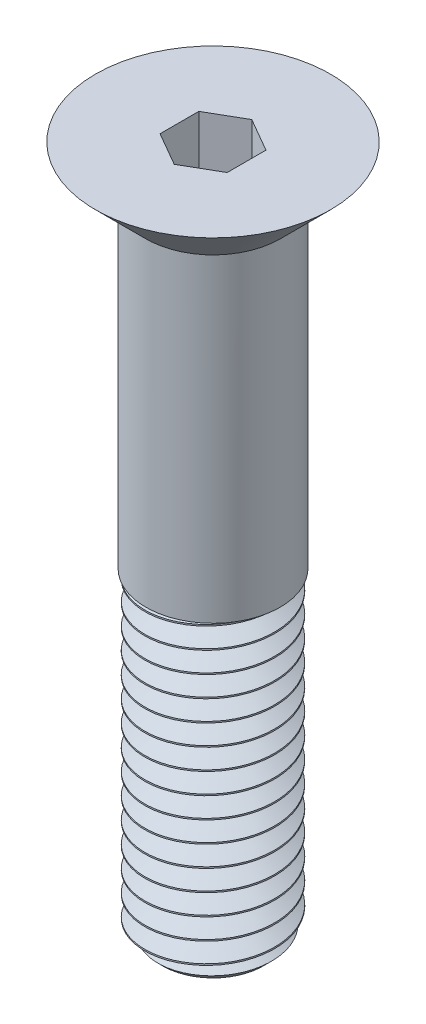
SolidWorks part; units mm, degrees
ref_plane "Front Plane" through (0, 0, 0) normal (0, 0, 1) x (1, 0, 0)
ref_plane "Top Plane" through (0, 0, 0) normal (0, 1, 0) x (1, 0, 0)
ref_plane "Right Plane" through (0, 0, 0) normal (1, 0, 0) x (0, 0, -1)
sketch "Sketch1" plane through (0, 0, 0) normal (0, 1, 0) x (1, 0, 0)
  circle A0 centre (0, 0) radius 4
  circle A1 centre (0, 0) radius 1
  dimension "D1" = 8
  dimension "D2" = 2
extrude "Boss-Extrude1" add sketch "Sketch1" along normal blind 19
ref_plane "Plane1" through (0, 29, 0) normal (0, 1, 0) x (1, 0, 0)
sketch "Sketch2" plane through (0, 29, 0) normal (0, 1, 0) x (1, 0, 0)
  circle A0 centre (0, 0) radius 4
  dimension "D1" = 8
curve "Helix/Spiral1" pitch 1.25 height 30 radius 4 centre (0, 29, 0) axis (0, -1, 0) start towards (0, 0, 1)
chamfer "Chamfer1" distance 1 angle 45 1 edges at (0, 0, 4)
sketch "Sketch3" plane through (0, 0, 0) normal (0, 0, 1) x (1, 0, 0)
  line L3 (-3.9386, 25.2152) -> (-3.9386, 25.8402) construction
  line L4 (-3.9386, 25.2152) -> (-3.9386, 24.5902) construction
  line L5 (-3.9386, 25.8402) -> (-3.9386, 24.5902)
  line L6 (-3.9386, 24.5902) -> (-2.8561, 25.2152)
  line L7 (-2.8561, 25.2152) -> (-3.9386, 25.8402)
  spline S0 degree 3 poles (-4, 29) (-4, 28.9741) (-3.7917, 28.9218) (-2.9021, 28.8438) (-1.5706, 28.7656) (0, 28.6875) (1.5706, 28.6094) (2.9021, 28.5313) (3.7917, 28.4531) (4.1041, 28.375) (3.7917, 28.2969) (2.9021, 28.2188) (1.5706, 28.1406) (0, 28.0625) (-1.5706, 27.9844) (-2.9021, 27.9063) (-3.7917, 27.8281) (-4.1041, 27.75) (-3.7917, 27.6719) (-2.9021, 27.5938) (-1.5706, 27.5156) (0, 27.4375) (1.5706, 27.3594) (2.9021, 27.2812) (3.7917, 27.2031) (4.1041, 27.125) (3.7917, 27.0469) (2.9021, 26.9688) (1.5706, 26.8906) (0, 26.8125) (-1.5706, 26.7344) (-2.9021, 26.6562) (-3.7917, 26.5781) (-4.1041, 26.5) (-3.7917, 26.4219) (-2.9021, 26.3437) (-1.5706, 26.2656) (0, 26.1875) (1.5706, 26.1094) (2.9021, 26.0312) (3.7917, 25.9531) (4.1041, 25.875) (3.7917, 25.7969) (2.9021, 25.7187) (1.5706, 25.6406) (0, 25.5625) (-1.5706, 25.4844) (-2.9021, 25.4062) (-3.7917, 25.3281) (-4.1041, 25.25) (-3.7917, 25.1719) (-2.9021, 25.0938) (-1.5706, 25.0156) (0, 24.9375) (1.5706, 24.8594) (2.9021, 24.7812) (3.7917, 24.7031) (4.1041, 24.625) (3.7917, 24.5469) (2.9021, 24.4688) (1.5706, 24.3906) (0, 24.3125) (-1.5706, 24.2344) (-2.9021, 24.1562) (-3.7917, 24.0781) (-4.1041, 24) (-3.7917, 23.9219) (-2.9021, 23.8437) (-1.5706, 23.7656) (0, 23.6875) (1.5706, 23.6094) (2.9021, 23.5312) (3.7917, 23.4531) (4.1041, 23.375) (3.7917, 23.2969) (2.9021, 23.2187) (1.5706, 23.1406) (0, 23.0625) (-1.5706, 22.9844) (-2.9021, 22.9062) (-3.7917, 22.8281) (-4.1041, 22.75) (-3.7917, 22.6719) (-2.9021, 22.5937) (-1.5706, 22.5156) (0, 22.4375) (1.5706, 22.3594) (2.9021, 22.2812) (3.7917, 22.2031) (4.1041, 22.125) (3.7917, 22.0469) (2.9021, 21.9688) (1.5706, 21.8906) (0, 21.8125) (-1.5706, 21.7344) (-2.9021, 21.6562) (-3.7917, 21.5781) (-4.1041, 21.5) (-3.7917, 21.4219) (-2.9021, 21.3438) (-1.5706, 21.2656) (0, 21.1875) (1.5706, 21.1094) (2.9021, 21.0312) (3.7917, 20.9531) (4.1041, 20.875) (3.7917, 20.7969) (2.9021, 20.7188) (1.5706, 20.6406) (0, 20.5625) (-1.5706, 20.4844) (-2.9021, 20.4062) (-3.7917, 20.3281) (-4.1041, 20.25) (-3.7917, 20.1719) (-2.9021, 20.0937) (-1.5706, 20.0156) (0, 19.9375) (1.5706, 19.8594) (2.9021, 19.7812) (3.7917, 19.7031) (4.1041, 19.625) (3.7917, 19.5469) (2.9021, 19.4687) (1.5706, 19.3906) (0, 19.3125) (-1.5706, 19.2344) (-2.9021, 19.1562) (-3.7917, 19.0781) (-4.1041, 19) (-3.7917, 18.9219) (-2.9021, 18.8437) (-1.5706, 18.7656) (0, 18.6875) (1.5706, 18.6094) (2.9021, 18.5312) (3.7917, 18.4531) (4.1041, 18.375) (3.7917, 18.2969) (2.9021, 18.2187) (1.5706, 18.1406) (0, 18.0625) (-1.5706, 17.9844) (-2.9021, 17.9062) (-3.7917, 17.8281) (-4.1041, 17.75) (-3.7917, 17.6719) (-2.9021, 17.5937) (-1.5706, 17.5156) (0, 17.4375) (1.5706, 17.3594) (2.9021, 17.2812) (3.7917, 17.2031) (4.1041, 17.125) (3.7917, 17.0469) (2.9021, 16.9687) (1.5706, 16.8906) (0, 16.8125) (-1.5706, 16.7344) (-2.9021, 16.6562) (-3.7917, 16.5781) (-4.1041, 16.5) (-3.7917, 16.4219) (-2.9021, 16.3437) (-1.5706, 16.2656) (0, 16.1875) (1.5706, 16.1094) (2.9021, 16.0312) (3.7917, 15.9531) (4.1041, 15.875) (3.7917, 15.7969) (2.9021, 15.7187) (1.5706, 15.6406) (0, 15.5625) (-1.5706, 15.4844) (-2.9021, 15.4062) (-3.7917, 15.3281) (-4.1041, 15.25) (-3.7917, 15.1719) (-2.9021, 15.0937) (-1.5706, 15.0156) (0, 14.9375) (1.5706, 14.8594) (2.9021, 14.7812) (3.7917, 14.7031) (4.1041, 14.625) (3.7917, 14.5469) (2.9021, 14.4687) (1.5706, 14.3906) (0, 14.3125) (-1.5706, 14.2344) (-2.9021, 14.1562) (-3.7917, 14.0781) (-4.1041, 14) (-3.7917, 13.9219) (-2.9021, 13.8437) (-1.5706, 13.7656) (0, 13.6875) (1.5706, 13.6094) (2.9021, 13.5312) (3.7917, 13.4531) (4.1041, 13.375) (3.7917, 13.2969) (2.9021, 13.2187) (1.5706, 13.1406) (0, 13.0625) (-1.5706, 12.9844) (-2.9021, 12.9062) (-3.7917, 12.8281) (-4.1041, 12.75) (-3.7917, 12.6719) (-2.9021, 12.5938) (-1.5706, 12.5156) (0, 12.4375) (1.5706, 12.3594) (2.9021, 12.2813) (3.7917, 12.2031) (4.1041, 12.125) (3.7917, 12.0469) (2.9021, 11.9688) (1.5706, 11.8906) (0, 11.8125) (-1.5706, 11.7344) (-2.9021, 11.6563) (-3.7917, 11.5781) (-4.1041, 11.5) (-3.7917, 11.4219) (-2.9021, 11.3438) (-1.5706, 11.2656) (0, 11.1875) (1.5706, 11.1094) (2.9021, 11.0313) (3.7917, 10.9531) (4.1041, 10.875) (3.7917, 10.7969) (2.9021, 10.7188) (1.5706, 10.6406) (0, 10.5625) (-1.5706, 10.4844) (-2.9021, 10.4063) (-3.7917, 10.3281) (-4.1041, 10.25) (-3.7917, 10.1719) (-2.9021, 10.0938) (-1.5706, 10.0156) (0, 9.9375) (1.5706, 9.8594) (2.9021, 9.7813) (3.7917, 9.7031) (4.1041, 9.625) (3.7917, 9.5469) (2.9021, 9.4688) (1.5706, 9.3906) (0, 9.3125) (-1.5706, 9.2344) (-2.9021, 9.1563) (-3.7917, 9.0781) (-4.1041, 9) (-3.7917, 8.9219) (-2.9021, 8.8438) (-1.5706, 8.7656) (0, 8.6875) (1.5706, 8.6094) (2.9021, 8.5313) (3.7917, 8.4531) (4.1041, 8.375) (3.7917, 8.2969) (2.9021, 8.2188) (1.5706, 8.1406) (0, 8.0625) (-1.5706, 7.9844) (-2.9021, 7.9063) (-3.7917, 7.8281) (-4.1041, 7.75) (-3.7917, 7.6719) (-2.9021, 7.5938) (-1.5706, 7.5156) (0, 7.4375) (1.5706, 7.3594) (2.9021, 7.2813) (3.7917, 7.2031) (4.1041, 7.125) (3.7917, 7.0469) (2.9021, 6.9688) (1.5706, 6.8906) (0, 6.8125) (-1.5706, 6.7344) (-2.9021, 6.6563) (-3.7917, 6.5781) (-4.1041, 6.5) (-3.7917, 6.4219) (-2.9021, 6.3438) (-1.5706, 6.2656) (0, 6.1875) (1.5706, 6.1094) (2.9021, 6.0313) (3.7917, 5.9531) (4.1041, 5.875) (3.7917, 5.7969) (2.9021, 5.7188) (1.5706, 5.6406) (0, 5.5625) (-1.5706, 5.4844) (-2.9021, 5.4063) (-3.7917, 5.3281) (-4.1041, 5.25) (-3.7917, 5.1719) (-2.9021, 5.0938) (-1.5706, 5.0156) (0, 4.9375) (1.5706, 4.8594) (2.9021, 4.7813) (3.7917, 4.7031) (4.1041, 4.625) (3.7917, 4.5469) (2.9021, 4.4688) (1.5706, 4.3906) (0, 4.3125) (-1.5706, 4.2344) (-2.9021, 4.1563) (-3.7917, 4.0781) (-4.1041, 4) (-3.7917, 3.9219) (-2.9021, 3.8438) (-1.5706, 3.7656) (0, 3.6875) (1.5706, 3.6094) (2.9021, 3.5313) (3.7917, 3.4531) (4.1041, 3.375) (3.7917, 3.2969) (2.9021, 3.2188) (1.5706, 3.1406) (0, 3.0625) (-1.5706, 2.9844) (-2.9021, 2.9063) (-3.7917, 2.8281) (-4.1041, 2.75) (-3.7917, 2.6719) (-2.9021, 2.5938) (-1.5706, 2.5156) (0, 2.4375) (1.5706, 2.3594) (2.9021, 2.2813) (3.7917, 2.2031) (4.1041, 2.125) (3.7917, 2.0469) (2.9021, 1.9688) (1.5706, 1.8906) (0, 1.8125) (-1.5706, 1.7344) (-2.9021, 1.6563) (-3.7917, 1.5781) (-4.1041, 1.5) (-3.7917, 1.4219) (-2.9021, 1.3438) (-1.5706, 1.2656) (0, 1.1875) (1.5706, 1.1094) (2.9021, 1.0313) (3.7917, 0.9531) (4.1041, 0.875) (3.7917, 0.7969) (2.9021, 0.7188) (1.5706, 0.6406) (0, 0.5625) (-1.5706, 0.4844) (-2.9021, 0.4063) (-3.7917, 0.3281) (-4.1041, 0.25) (-3.7917, 0.1719) (-2.9021, 0.0937) (-1.5706, 0.0156) (0, -0.0625) (1.5706, -0.1406) (2.9021, -0.2188) (3.7917, -0.2969) (4.1041, -0.375) (3.7917, -0.4531) (2.9021, -0.5313) (1.5706, -0.6094) (0, -0.6875) (-1.5706, -0.7656) (-2.9021, -0.8438) (-3.7917, -0.9218) (-4, -0.9741) (-4, -1) knots 0 0 0 0 0.002604 0.005208 0.007812 0.010417 0.013021 0.015625 0.018229 0.020833 0.023437 0.026042 0.028646 0.03125 0.033854 0.036458 0.039062 0.041667 0.044271 0.046875 0.049479 0.052083 0.054687 0.057292 0.059896 0.0625 0.065104 0.067708 0.070312 0.072917 0.075521 0.078125 0.080729 0.083333 0.085937 0.088542 0.091146 0.09375 0.096354 0.098958 0.101562 0.104167 0.106771 0.109375 0.111979 0.114583 0.117187 0.119792 0.122396 0.125 0.127604 0.130208 0.132812 0.135417 0.138021 0.140625 0.143229 0.145833 0.148437 0.151042 0.153646 0.15625 0.158854 0.161458 0.164062 0.166667 0.169271 0.171875 0.174479 0.177083 0.179687 0.182292 0.184896 0.1875 0.190104 0.192708 0.195312 0.197917 0.200521 0.203125 0.205729 0.208333 0.210937 0.213542 0.216146 0.21875 0.221354 0.223958 0.226562 0.229167 0.231771 0.234375 0.236979 0.239583 0.242187 0.244792 0.247396 0.25 0.252604 0.255208 0.257812 0.260417 0.263021 0.265625 0.268229 0.270833 0.273437 0.276042 0.278646 0.28125 0.283854 0.286458 0.289062 0.291667 0.294271 0.296875 0.299479 0.302083 0.304687 0.307292 0.309896 0.3125 0.315104 0.317708 0.320312 0.322917 0.325521 0.328125 0.330729 0.333333 0.335937 0.338542 0.341146 0.34375 0.346354 0.348958 0.351562 0.354167 0.356771 0.359375 0.361979 0.364583 0.367187 0.369792 0.372396 0.375 0.377604 0.380208 0.382812 0.385417 0.388021 0.390625 0.393229 0.395833 0.398437 0.401042 0.403646 0.40625 0.408854 0.411458 0.414062 0.416667 0.419271 0.421875 0.424479 0.427083 0.429687 0.432292 0.434896 0.4375 0.440104 0.442708 0.445312 0.447917 0.450521 0.453125 0.455729 0.458333 0.460937 0.463542 0.466146 0.46875 0.471354 0.473958 0.476562 0.479167 0.481771 0.484375 0.486979 0.489583 0.492187 0.494792 0.497396 0.5 0.502604 0.505208 0.507812 0.510417 0.513021 0.515625 0.518229 0.520833 0.523437 0.526042 0.528646 0.53125 0.533854 0.536458 0.539062 0.541667 0.544271 0.546875 0.549479 0.552083 0.554687 0.557292 0.559896 0.5625 0.565104 0.567708 0.570312 0.572917 0.575521 0.578125 0.580729 0.583333 0.585937 0.588542 0.591146 0.59375 0.596354 0.598958 0.601562 0.604167 0.606771 0.609375 0.611979 0.614583 0.617187 0.619792 0.622396 0.625 0.627604 0.630208 0.632812 0.635417 0.638021 0.640625 0.643229 0.645833 0.648437 0.651042 0.653646 0.65625 0.658854 0.661458 0.664062 0.666667 0.669271 0.671875 0.674479 0.677083 0.679687 0.682292 0.684896 0.6875 0.690104 0.692708 0.695312 0.697917 0.700521 0.703125 0.705729 0.708333 0.710937 0.713542 0.716146 0.71875 0.721354 0.723958 0.726562 0.729167 0.731771 0.734375 0.736979 0.739583 0.742187 0.744792 0.747396 0.75 0.752604 0.755208 0.757812 0.760417 0.763021 0.765625 0.768229 0.770833 0.773437 0.776042 0.778646 0.78125 0.783854 0.786458 0.789062 0.791667 0.794271 0.796875 0.799479 0.802083 0.804687 0.807292 0.809896 0.8125 0.815104 0.817708 0.820312 0.822917 0.825521 0.828125 0.830729 0.833333 0.835937 0.838542 0.841146 0.84375 0.846354 0.848958 0.851562 0.854167 0.856771 0.859375 0.861979 0.864583 0.867187 0.869792 0.872396 0.875 0.877604 0.880208 0.882812 0.885417 0.888021 0.890625 0.893229 0.895833 0.898437 0.901042 0.903646 0.90625 0.908854 0.911458 0.914062 0.916667 0.919271 0.921875 0.924479 0.927083 0.929687 0.932292 0.934896 0.9375 0.940104 0.942708 0.945312 0.947917 0.950521 0.953125 0.955729 0.958333 0.960937 0.963542 0.966146 0.96875 0.971354 0.973958 0.976562 0.979167 0.981771 0.984375 0.986979 0.989583 0.992187 0.994792 0.997396 1 1 1 1 construction
  dimension "D1" = 1.0825
sweep "Cut-Sweep1" cut profiles "Sketch3" path "Helix/Spiral1" align with end faces yes
sketch "Sketch5" plane through (0, 0, 0) normal (0, 0, 1) x (1, 0, 0)
  line L0 (0, 0) -> (0, 41) construction
  line L1 (0, 41) -> (7, 41)
  line L2 (7, 41) -> (4, 38)
  line L3 (4, 38) -> (4, 19)
  line L4 (4, 19) -> (0, 19)
  line L5 (3.8924, 19) -> (-2.8105, 19) construction
  line L6 (0, 19) -> (0, 41)
  dimension "D1" = 45
  dimension "D2" = 4
  dimension "D3" = 19
  dimension "D4" = 7
revolve "Revolve1" add sketch "Sketch5" angle 360 about L0
sketch "Sketch6" plane through (0, 41, 0) normal (0, 1, 0) x (1, 0, 0)
  line L1 (0, 2.3094) -> (-2, 1.1547)
  line L2 (-2, 1.1547) -> (-2, -1.1547)
  line L3 (-2, -1.1547) -> (0, -2.3094)
  line L4 (0, -2.3094) -> (2, -1.1547)
  line L5 (2, -1.1547) -> (2, 1.1547)
  line L6 (2, 1.1547) -> (0, 2.3094)
  circle A0 centre (0, 0) radius 2 construction
  dimension "D1" = 4
extrude "Cut-Extrude1" cut sketch "Sketch6" against normal blind 5
sketch "Sketch7" plane through (0, 0, 0) normal (0, -1, 0) x (1, 0, 0)
  circle A0 centre (0, 0) radius 1
extrude "Cut-Extrude2" cut sketch "Sketch7" against normal blind 20.5
chamfer "Chamfer2" distance 2 angle 45 1 edges at (0, 0, 1)
sketch "Sketch8" plane through (0, 19, 0) normal (0, -1, 0) x (1, 0, 0)
  circle A0 centre (0, 0) radius 4
  circle A1 centre (0, 0) radius 3.8647
  circle A2 centre (0, 0) radius 4 construction
  dimension "D1" = 0.1353
extrude "Cut-Extrude3" cut sketch "Sketch8" along normal through all
